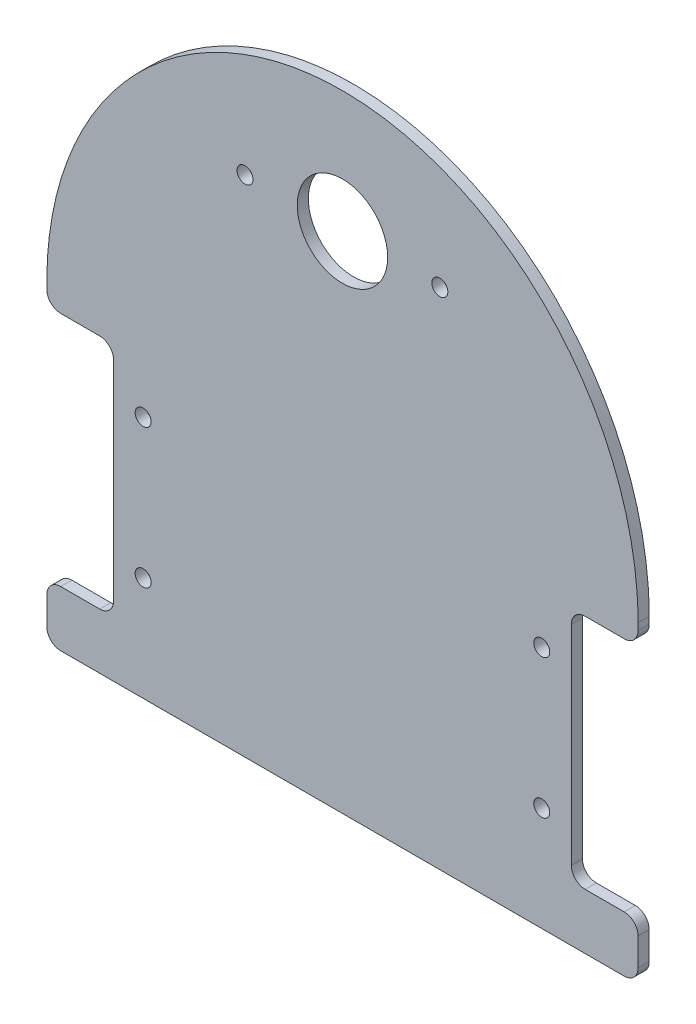
SolidWorks part; units mm, degrees
material "A-Glass Fiber"
ref_plane "Top Plane" through (0, 0, 0) normal (0, 0, 1) x (1, 0, 0)
ref_plane "Right Plane" through (0, 0, 0) normal (0, 1, 0) x (1, 0, 0)
ref_plane "Front Plane" through (0, 0, 0) normal (1, 0, 0) x (0, 0, -1)
sketch "Sketch1" plane through (0, 0, 0) normal (0, 0, 1) x (1, 0, 0)
  line L1 (42.5, -45) -> (-42.5, -45)
  line L2 (42.5, -45) -> (42.5, 45)
  line L3 (42.5, 45) -> (-42.5, 45)
  line L4 (-42.5, -45) -> (-42.5, 45)
  line L5 (42.5, -45) -> (-42.5, 45) construction
  line L6 (42.5, 45) -> (-42.5, -45) construction
  point P0 (0, 0)
  dimension "D1" = 85
  dimension "D2" = 90
extrude "Boss-Extrude1" add sketch "Sketch1" along normal blind 1.6
sketch "Sketch2" plane through (0, 0, 1.6) normal (0, 0, 1) x (1, 0, 0)
  line L0 (-42.5, 45) -> (-42.5, -45) construction
  line L1 (42.5, 45) -> (-42.5, 45) construction
  line L6 (-42.5, 0) -> (-70, 0)
  line L7 (-70, 0) -> (-70, 70)
  line L8 (42.5, -45) -> (42.5, 45) construction
  line L9 (-70, 70) -> (70, 70)
  line L10 (70, 70) -> (70, 0)
  line L11 (70, 0) -> (42.5, 0)
  ellipse E0 centre (0, 0) end of major axis (0, -45) minor radius 42.5 (42.5, 0) -> (-42.5, 0) ccw
  point P14 (0, 70)
  dimension "D1" = 140
  dimension "D2" = 70
extrude "Cut-Extrude1" cut sketch "Sketch2" against normal through all
sketch "Sketch3" plane through (0, 0, 1.6) normal (0, 0, 1) x (1, 0, 0)
  line L1 (-42.5, -3) -> (-32.9, -3)
  line L2 (-42.5, -3) -> (-42.5, -37)
  line L3 (-42.5, -37) -> (-32.9, -37)
  line L4 (-32.9, -3) -> (-32.9, -37)
  line L6 (0, -0.88) -> (0, 0.88) construction
  line L7 (42.5, -3) -> (32.9, -3)
  line L8 (42.5, -37) -> (32.9, -37)
  line L9 (32.9, -3) -> (32.9, -37)
  line L10 (42.5, -3) -> (42.5, -37)
  line L11 (-42.5, 0) -> (-42.5, -45) construction
  line L13 (-42.5, -45) -> (42.5, -45) construction
  dimension "D1" = 9.6
  dimension "D2" = 34
  dimension "D3" = 8
extrude "Cut-Extrude2" cut sketch "Sketch3" against normal through all
sketch "Sketch4" plane through (0, 0, 1.6) normal (0, 0, 1) x (1, 0, 0)
  line L0 (-42.5, -45) -> (42.5, -45) construction
  circle A0 centre (0, 27.5) radius 6.5
  dimension "D1" = 13
  dimension "D2" = 72.5
extrude "Cut-Extrude3" cut sketch "Sketch4" against normal through all
sketch "Sketch5" plane through (0, 0, 1.6) normal (0, 0, 1) x (1, 0, 0)
  line L1 (-32.9, -37) -> (-32.9, -3) construction
  line L2 (-28.65, -10) -> (-28.65, -30) construction
  line L3 (0, -0.88) -> (0, 0.88) construction
  line L4 (-1016.15, -20) -> (48983.85, -20) construction
  line L5 (0, -1000) -> (0, 49000) construction
  circle A0 centre (-28.65, -10) radius 1.15
  circle A1 centre (-28.65, -30) radius 1.15
  circle A2 centre (28.65, -30) radius 1.15
  circle A3 centre (28.65, -10) radius 1.15
  point P2 (-28.65, -20)
  point P14 (-32.9, -20)
  dimension "D3" = 2.3
  dimension "D1" = 4.25
  dimension "D2" = 20
extrude "Cut-Extrude4" cut sketch "Sketch5" against normal through all
sketch "Sketch6" plane through (0, 0, 1.6) normal (0, 0, 1) x (1, 0, 0)
  line L0 (-14, 27.5) -> (14, 27.5) construction
  circle A1 centre (-14, 27.5) radius 1.15
  circle A2 centre (14, 27.5) radius 1.15
  point P5 (0, 27.5)
  dimension "D2" = 2.3
  dimension "D1" = 28
extrude "Cut-Extrude5" cut sketch "Sketch6" against normal through all
fillet "Fillet1" radius 2 10 edges at (42.5, -37, 0.8) (32.9, -37, 0.8) (32.9, -3, 0.8) (42.5, -3, 0.8) (-32.9, -37, 0.8) (-32.9, -3, 0.8) (-42.5, -37, 0.8) (-42.5, -3, 0.8) (42.5, -45, 0.8) (-42.5, -45, 0.8)
equation "\"Motor_Position\"= 8"
equation "\"D3@Sketch3\"=\"Motor_Position\""
equation "\"Caster_Position\"= 72.5"
equation "\"D2@Sketch4\"=\"Caster_Position\""
